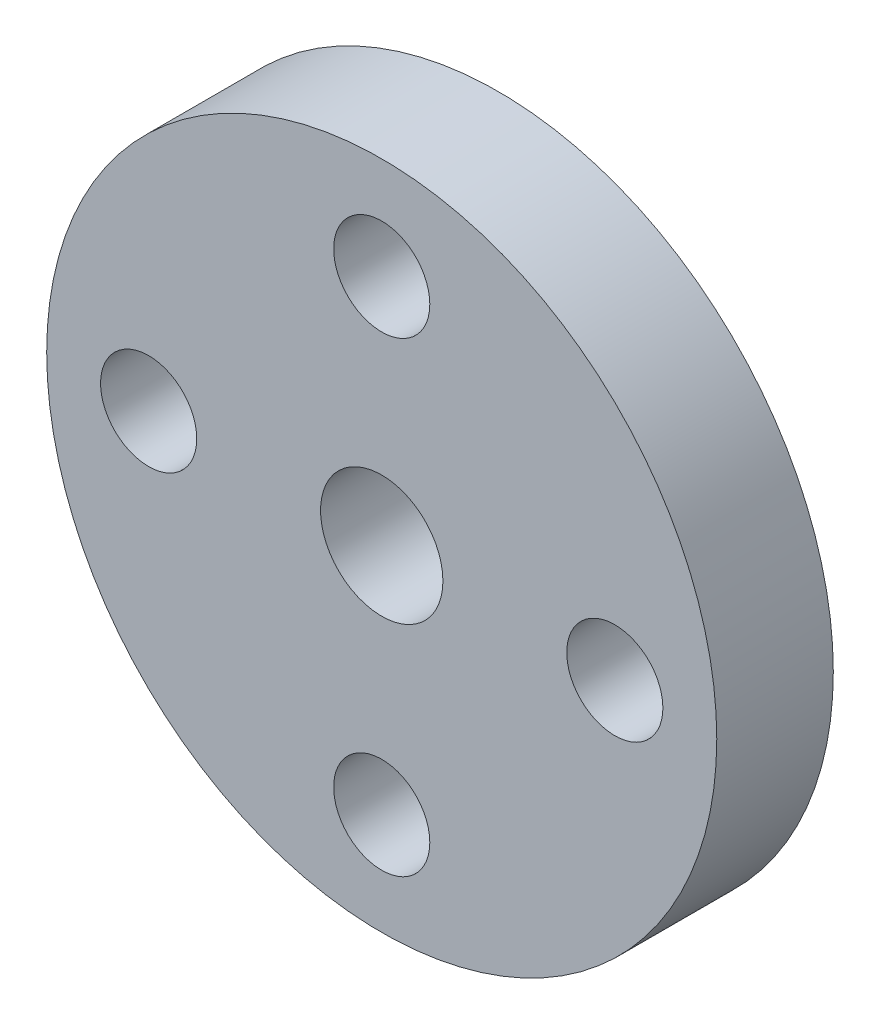
SolidWorks part; units mm, degrees
material "ABS"
ref_plane "前基準面" through (0, 0, 0) normal (0, 0, 1) x (1, 0, 0)
ref_plane "上基準面" through (0, 0, 0) normal (0, 1, 0) x (1, 0, 0)
ref_plane "右基準面" through (0, 0, 0) normal (1, 0, 0) x (0, 0, -1)
sketch "草圖1" plane through (0, 0, 0) normal (0, 0, 1) x (1, 0, 0)
  circle A0 centre (0, 0) radius 11.5
  circle A1 centre (0, 0) radius 8 construction
  circle A2 centre (0, 8) radius 1.65
  circle A3 centre (8, 0) radius 1.65
  circle A4 centre (0, -8) radius 1.65
  circle A5 centre (-8, 0) radius 1.65
  circle A6 centre (0, 0) radius 2.1
  dimension "D1" = 23
  dimension "D2" = 16
  dimension "D3" = 3.3
  dimension "D5" = 8
  dimension "D6" = 4.2
  dimension "D4" = 4
extrude "填料-伸長1" add sketch "草圖1" along normal blind 4
